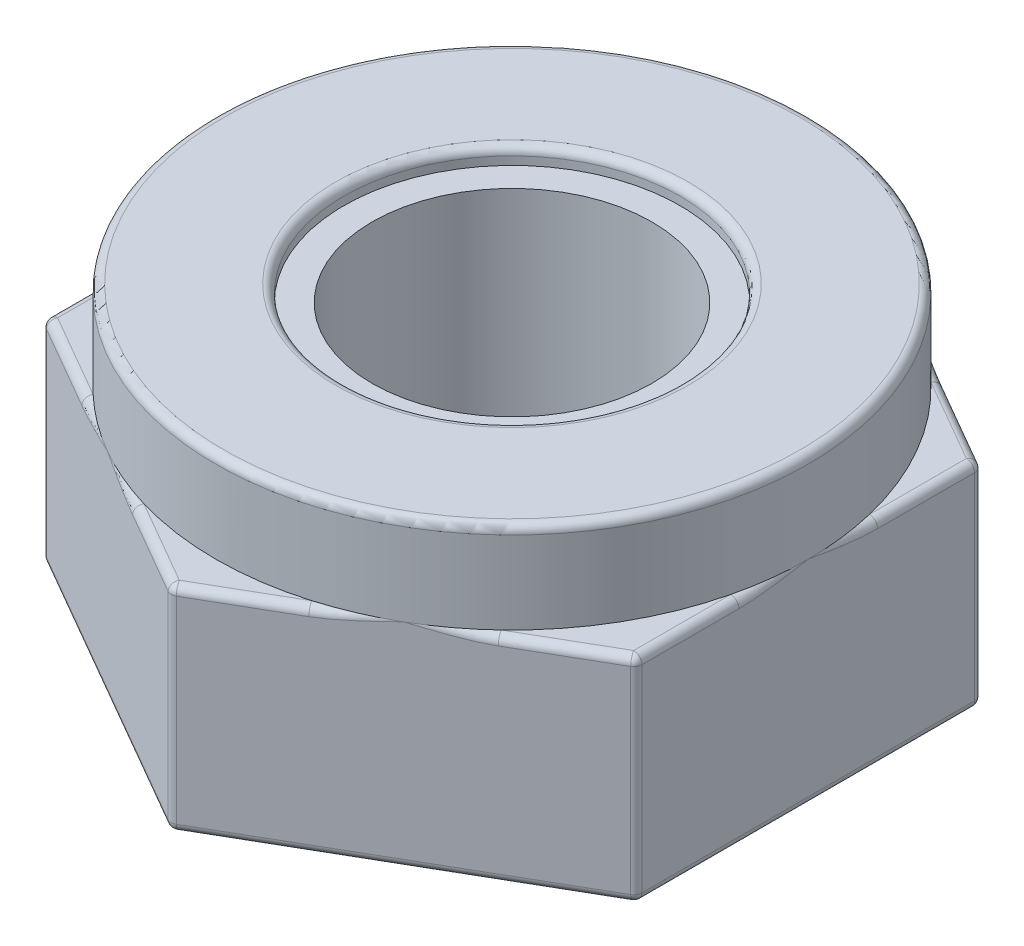
SolidWorks part; units mm, degrees
ref_plane "前视基准面" through (0, 0, 0) normal (0, 0, 1) x (1, 0, 0)
ref_plane "上视基准面" through (0, 0, 0) normal (0, 1, 0) x (1, 0, 0)
ref_plane "右视基准面" through (0, 0, 0) normal (1, 0, 0) x (0, 0, -1)
sketch "草图1" plane through (0, 0, 0) normal (0, 1, 0) x (1, 0, 0)
  line L1 (0, -4.1569) -> (3.6, -2.0785)
  line L2 (3.6, -2.0785) -> (3.6, 2.0785)
  line L3 (3.6, 2.0785) -> (0, 4.1569)
  line L4 (0, 4.1569) -> (-3.6, 2.0785)
  line L5 (-3.6, 2.0785) -> (-3.6, -2.0785)
  line L6 (-3.6, -2.0785) -> (0, -4.1569)
  circle A0 centre (0, 0) radius 1.7
  circle A1 centre (0, 0) radius 3.6 construction
  dimension "D2" = 3.4
  dimension "D1" = 7.2
extrude "凸台-拉伸1" add sketch "草图1" along normal blind 2.6
sketch "草图2" plane through (0, 0, 0) normal (0, -1, 0) x (1, 0, 0)
  circle A0 centre (0, 0) radius 1.7
  circle A1 centre (0, 0) radius 3.6
extrude "凸台-拉伸2" add sketch "草图2" against normal blind 3.7
sketch "草图3" plane through (0, 3.7, 0) normal (0, 1, 0) x (1, 0, 0)
  circle A0 centre (0, 0) radius 2.0423
  circle A1 centre (0, 0) radius 1.7
extrude "切除-拉伸1" cut sketch "草图3" against normal blind 0.2
fillet "圆角1" radius 0.1 26 edges at (0, 3.7, -3.6) (1.8, 0, -3.1177) (2.7, 2.6, -2.5981) (0.9, 2.6, -3.6373) (-1.8, 0, -3.1177) (0, 1.3, -4.1569) (-0.9, 2.6, -3.6373) (-2.7, 2.6, -2.5981) (1.8, 0, 3.1177) (0.9, 2.6, 3.6373) (2.7, 2.6, 2.5981) (3.6, 1.3, -2.0785) (3.6, 0, 0) (3.6, 1.3, 2.0785) (3.6, 2.6, 1.0392) (3.6, 2.6, -1.0392) (-3.6, 0, 0) (-3.6, 1.3, -2.0785) (-3.6, 2.6, -1.0392) (-3.6, 2.6, 1.0392) (0, 1.3, 4.1569) (-1.8, 0, 3.1177) (-3.6, 1.3, 2.0785) (-2.7, 2.6, 2.5981) (-0.9, 2.6, 3.6373) (0, 3.7, 2.0423)
